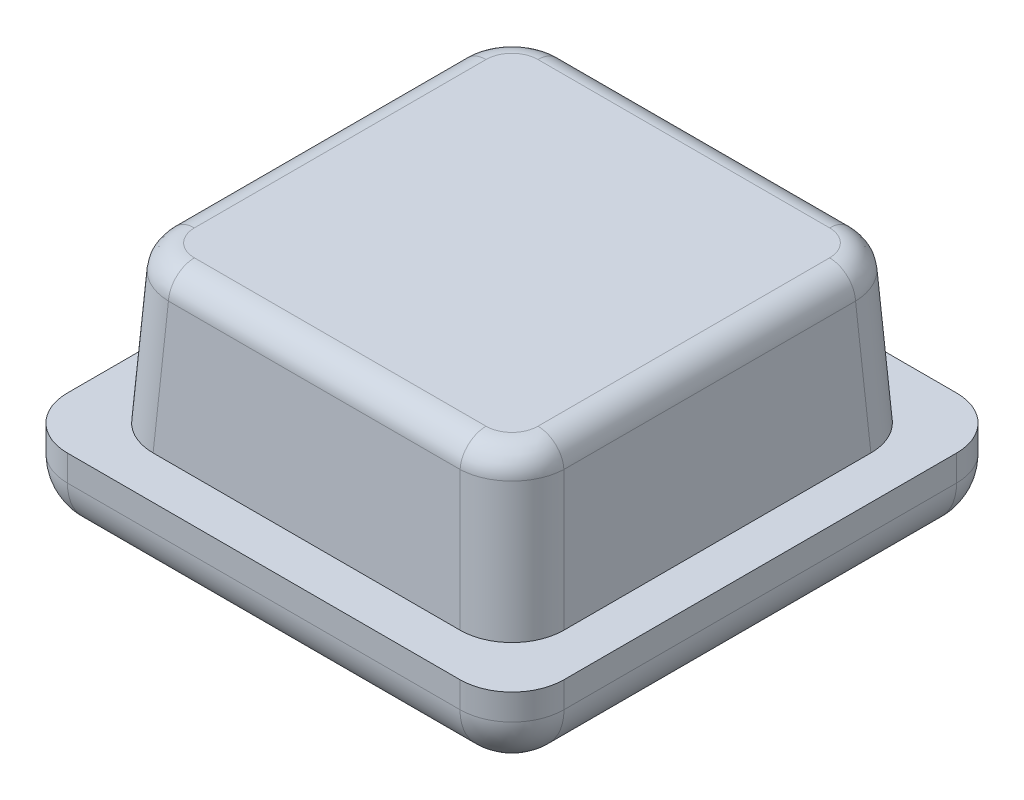
SolidWorks part; units mm, degrees
ref_plane "Front Plane" through (0, 0, 0) normal (0, 0, 1) x (1, 0, 0)
ref_plane "Top Plane" through (0, 0, 0) normal (0, 1, 0) x (1, 0, 0)
ref_plane "Right Plane" through (0, 0, 0) normal (1, 0, 0) x (0, 0, -1)
sketch "Sketch1" plane through (0, 0, 0) normal (0, 1, 0) x (1, 0, 0)
  line L1 (0, 0) -> (19.1, 0)
  line L2 (0, 0) -> (0, 19.1)
  line L3 (0, 19.1) -> (19.1, 19.1)
  line L4 (19.1, 0) -> (19.1, 19.1)
  dimension "D1" = 19.1
extrude "Boss-Extrude1" add sketch "Sketch1" along normal blind 3
sketch "Sketch2" plane through (0, 3, 0) normal (0, 1, 0) x (1, 0, 0)
  line L8 (1.65, 1.65) -> (17.45, 1.65)
  line L9 (17.45, 1.65) -> (17.45, 17.45)
  line L10 (1.65, 17.45) -> (1.65, 1.65)
  line L11 (17.45, 17.45) -> (1.65, 17.45)
  line L12 (1.65, 1.65) -> (17.45, 1.65)
  line L13 (17.45, 1.65) -> (17.45, 17.45)
  line L14 (1.65, 17.45) -> (1.65, 1.65)
  line L15 (17.45, 17.45) -> (1.65, 17.45)
  dimension "D1" = 1.65
ref_plane "Plane1" through (0, 9, 0) normal (0, 1, 0) x (1, 0, 0)
sketch "Sketch3" plane through (0, 9, 0) normal (0, 1, 0) x (1, 0, 0)
  line L8 (2, 2) -> (17.1, 2)
  line L9 (2, 17.1) -> (2, 2)
  line L10 (17.1, 17.1) -> (2, 17.1)
  line L11 (17.1, 2) -> (17.1, 17.1)
  line L12 (2, 2) -> (17.1, 2)
  line L13 (2, 17.1) -> (2, 2)
  line L14 (17.1, 17.1) -> (2, 17.1)
  line L15 (17.1, 2) -> (17.1, 17.1)
  dimension "D1" = 2
loft "Loft1" add profiles "Sketch2", "Sketch3" connector at (17.45, 3, -17.45) connector at (17.1, 9, -17.1)
ref_plane "Plane2" through (9.55, 0, 0) normal (1, 0, 0) x (0, 0, -1)
ref_plane "Plane3" through (0, 0, -9.55) normal (0, 0, 1) x (1, 0, 0)
fillet "Fillet1" radius 2 8 edges at (19.1, 1.5, 0) (0, 1.5, 0) (19.1, 1.5, -19.1) (0, 1.5, -19.1)
fillet "Fillet2" radius 1 8 edges
fillet "Fillet3" radius 2 8 edges at (0.5858, 0, -0.5858) (0, 0, -9.55) (0.5858, 0, -18.5142) (9.55, 0, -19.1) (18.5142, 0, -18.5142) (19.1, 0, -9.55) (18.5142, 0, -0.5858) (9.55, 0, 0)
